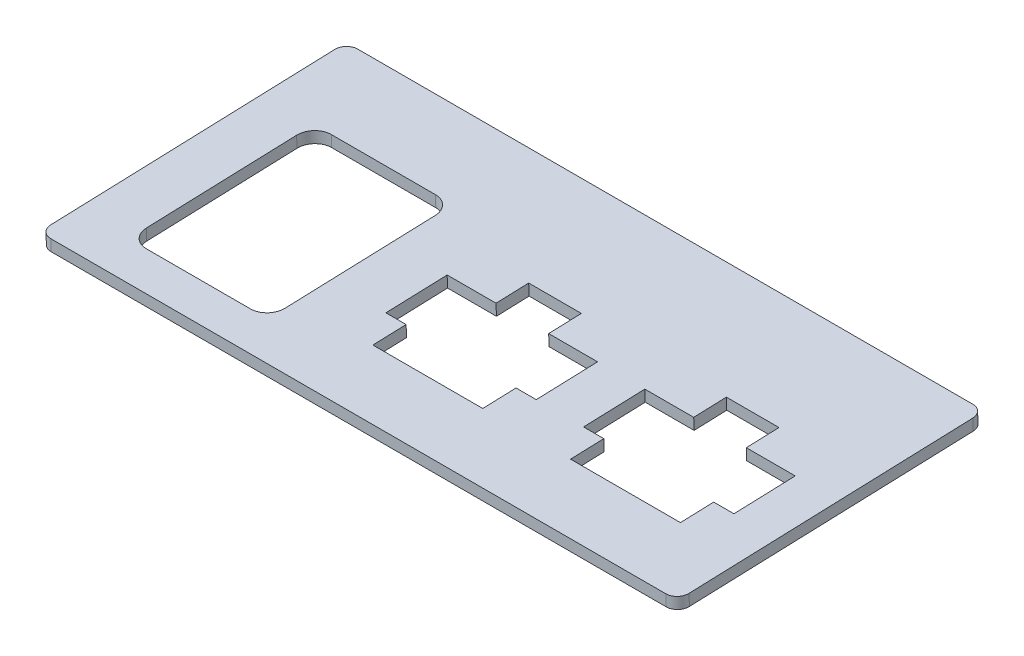
SolidWorks part; units mm, degrees
ref_plane "Front Plane" through (0, 0, 0) normal (0, 0, 1) x (1, 0, 0)
ref_plane "Top Plane" through (0, 0, 0) normal (0, 1, 0) x (1, 0, 0)
ref_plane "Right Plane" through (0, 0, 0) normal (1, 0, 0) x (0, 0, -1)
sketch "Sketch1" plane through (0, -71.9872, -2.5138) normal (0, 0.9994, 0.0349) x (1, 0, 0)
  line L1 (-53.6759, -2.9116) -> (-56.175, -2.9116) construction
  line L2 (55.275, 48.6897) -> (-55.275, 48.6897) construction
  line L8 (-55.175, -4.4116) -> (55.175, -4.4116)
  line L9 (55.175, -4.4116) -> (55.175, 48.6897)
  line L10 (55.175, 48.6897) -> (-55.175, 48.6897)
  line L11 (-55.175, 48.6897) -> (-55.175, -4.4116)
  dimension "D1" = 1.5
  dimension "D2" = 3.0034
  dimension "D3" = 3.0034
extrude "Boss-Extrude1" add sketch "Sketch1" along normal blind 2
sketch "Sketch2" plane through (0, -71.9872, -2.5138) normal (0, -0.9994, -0.0349) x (1, 0, 0)
  line L0 (-4.05, -23.4641) -> (-4.05, -29.1141)
  line L1 (-43.175, -2.1141) -> (-25.175, -2.1141)
  line L2 (-46.175, -5.1141) -> (-46.175, -31.1141)
  line L3 (-43.175, -34.1141) -> (-25.175, -34.1141)
  line L4 (-22.175, -5.1141) -> (-22.175, -31.1141)
  line L5 (-12.5, -12.8641) -> (-9, -12.8641)
  line L6 (-12.5, -12.8641) -> (-12.5, -23.4641)
  line L7 (-12.5, -23.4641) -> (-4.05, -23.4641)
  line L8 (13.5, -12.8641) -> (13.5, -23.4641)
  line L9 (-9, -7.1141) -> (10, -7.1141)
  line L10 (-9, -7.1141) -> (-9, -12.8641)
  line L11 (-4.05, -29.1141) -> (5.05, -29.1141)
  line L12 (10, -7.1141) -> (10, -12.8641)
  line L13 (10, -12.8641) -> (13.5, -12.8641)
  line L14 (5.05, -23.4641) -> (5.05, -29.1141)
  line L15 (5.05, -23.4641) -> (13.5, -23.4641)
  line L16 (-13, -4.6141) -> (14, -31.6141) construction
  line L17 (-13, -4.6141) -> (14, -4.6141) construction
  line L18 (-13, -4.6141) -> (-13, -31.6141) construction
  line L19 (-13, -31.6141) -> (14, -31.6141) construction
  line L20 (14, -4.6141) -> (14, -31.6141) construction
  line L21 (17.5875, 3.7502) -> (17.5875, -36.664) construction
  line L22 (47.675, -18.1641) -> (21.675, -18.1641) construction
  line L23 (34.675, -7.1141) -> (34.675, -29.1141) construction
  line L24 (21.175, -4.6141) -> (21.175, -31.6141) construction
  line L25 (48.175, -31.6141) -> (21.175, -31.6141) construction
  line L26 (48.175, -4.6141) -> (48.175, -31.6141) construction
  line L27 (48.175, -4.6141) -> (21.175, -4.6141) construction
  line L28 (-48.175, -18.1141) -> (-46.175, -18.1141) construction
  line L29 (-48.175, -0.1141) -> (-20.175, -0.1141) construction
  line L30 (-48.175, -0.1141) -> (-48.175, -36.1141) construction
  line L31 (-48.175, -36.1141) -> (-20.175, -36.1141) construction
  line L32 (-20.175, -0.1141) -> (-20.175, -36.1141) construction
  line L33 (-34.175, -2.1141) -> (-34.175, -0.1141) construction
  line L34 (0.5, -7.1141) -> (0.5, -29.1141) construction
  line L35 (-12.5, -18.1641) -> (13.5, -18.1641) construction
  line L36 (48.175, -4.6141) -> (21.175, -31.6141) construction
  line L37 (30.125, -23.4641) -> (21.675, -23.4641)
  line L38 (30.125, -23.4641) -> (30.125, -29.1141)
  line L39 (25.175, -12.8641) -> (21.675, -12.8641)
  line L40 (25.175, -7.1141) -> (25.175, -12.8641)
  line L41 (39.225, -29.1141) -> (30.125, -29.1141)
  line L42 (44.175, -7.1141) -> (44.175, -12.8641)
  line L43 (44.175, -7.1141) -> (25.175, -7.1141)
  line L44 (21.675, -12.8641) -> (21.675, -23.4641)
  line L45 (47.675, -23.4641) -> (39.225, -23.4641)
  line L46 (47.675, -12.8641) -> (47.675, -23.4641)
  line L47 (47.675, -12.8641) -> (44.175, -12.8641)
  line L48 (39.225, -23.4641) -> (39.225, -29.1141)
  line L49 (21.175, -18.1141) -> (14, -18.1141) construction
  line L50 (-55.175, 4.4116) -> (55.175, 4.4116) construction
  line L51 (48.175, -18.1141) -> (52.175, -18.1141) construction
  line L52 (55.175, 4.4116) -> (55.175, -48.6897) construction
  line L53 (-46.7914, -40.6398) -> (46.7914, -40.6398) construction
  line L54 (-13, -18.1141) -> (-20.175, -18.1141) construction
  line L55 (-34.175, -0.1141) -> (-34.175, 4.4116) construction
  line L56 (-34.175, -36.1141) -> (-34.175, -40.6398) construction
  line L57 (-55.175, -48.6897) -> (-55.175, 4.4116) construction
  line L58 (-48.175, -18.1141) -> (-52.175, -18.1141) construction
  arc A0 (-46.175, -31.1141) -> (-43.175, -34.1141) centre (-43.175, -31.1141) ccw
  arc A1 (-25.175, -34.1141) -> (-22.175, -31.1141) centre (-25.175, -31.1141) ccw
  arc A2 (-25.175, -2.1141) -> (-22.175, -5.1141) centre (-25.175, -5.1141) cw
  arc A3 (-43.175, -2.1141) -> (-46.175, -5.1141) centre (-43.175, -5.1141) ccw
  point P28 (0.5, -18.1141)
  point P63 (34.675, -18.1141)
  dimension "D1" = 3
  dimension "D2" = 32
  dimension "D3" = 24
  dimension "D4" = 28
  dimension "D5" = 36
  dimension "D6" = 26
  dimension "D7" = 22
  dimension "D8" = 10.6
  dimension "D9" = 19
  dimension "D10" = 9.1
  dimension "D11" = 5.75
  dimension "D12" = 27
  dimension "D13" = 27
  dimension "D14" = 4
  dimension "D15" = 3
  dimension "D16" = 3
extrude "Cut-Extrude1" cut sketch "Sketch2" against normal up to next
fillet "Fillet1" radius 2 4 edges at (-55.175, -71.1418, 1.93) (55.175, -71.1418, 1.93) (55.175, -69.2886, -51.139) (-55.175, -69.2886, -51.139)
